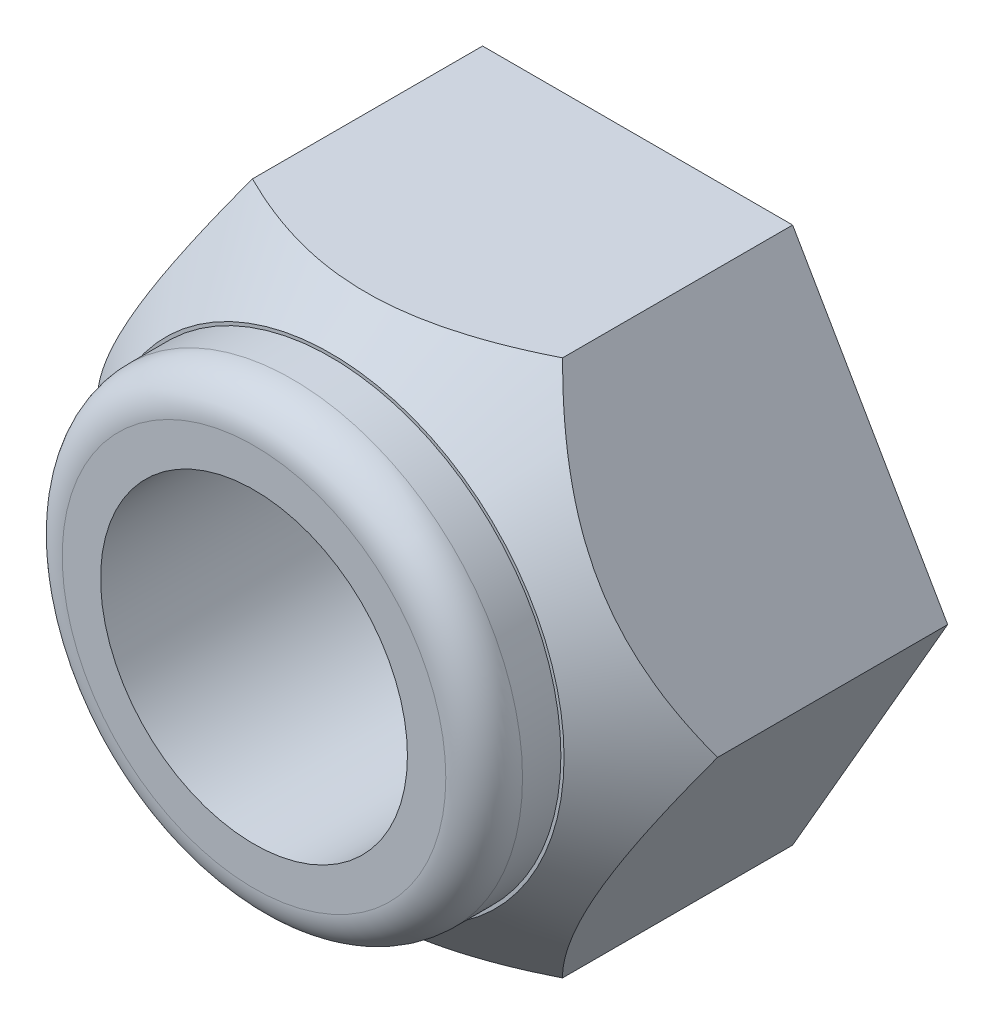
SolidWorks part; units mm, degrees
material "AISI 304"
ref_plane "前视基准面" through (0, 0, 0) normal (0, 0, 1) x (1, 0, 0)
ref_plane "上视基准面" through (0, 0, 0) normal (0, 1, 0) x (1, 0, 0)
ref_plane "右视基准面" through (0, 0, 0) normal (1, 0, 0) x (0, 0, -1)
other "Configuration Table"
sketch "草图1" plane through (0, 0, 0) normal (0, 0, 1) x (1, 0, 0)
  line L1 (4.0415, 0) -> (2.0207, 3.5)
  line L2 (2.0207, 3.5) -> (-2.0207, 3.5)
  line L3 (-2.0207, 3.5) -> (-4.0415, 0)
  line L4 (-4.0415, 0) -> (-2.0207, -3.5)
  line L5 (-2.0207, -3.5) -> (2.0207, -3.5)
  line L6 (2.0207, -3.5) -> (4.0415, 0)
  circle A0 centre (0, 0) radius 3.5 construction
extrude "凸台-拉伸1" add sketch "草图1" along normal blind 4
sketch "草图2" plane through (0, 0, 4) normal (0, 0, 1) x (1, 0, 0)
  circle A0 centre (0, 0) radius 3
  circle A1 centre (0, 0) radius 2
  dimension "D1" = 6
  dimension "D2" = 4
extrude "凸台-拉伸2" add sketch "草图2" along normal blind 1 contours A0
extrude "切除-拉伸1" cut sketch "草图2<3>" against normal mid plane 11 contours A1
sketch "草图2<3>" plane through (0, 0, 4) normal (0, 0, 1) x (1, 0, 0) same geometry as "草图2"
sketch "草图3" plane through (0, 0, 0) normal (0, 1, 0) x (1, 0, 0)
  line L0 (-4.0415, -4) -> (-4.0415, -3)
  line L1 (-4.0415, -4) -> (-4.0415, 0) construction
  line L2 (-4.0415, -3) -> (-3.0415, -4)
  line L3 (-2.0207, -4) -> (-4.0415, -4) construction
  line L4 (-3.0415, -4) -> (-4.0415, -4)
  line L5 (0, 0) -> (0, 50000) construction
  dimension "D1" = 1
  dimension "D2" = 1
revolve "切除-旋转1" cut sketch "草图3" angle 360 about L5
fillet "圆角3" radius 0.5 1 edges at (3, 0, 5)
